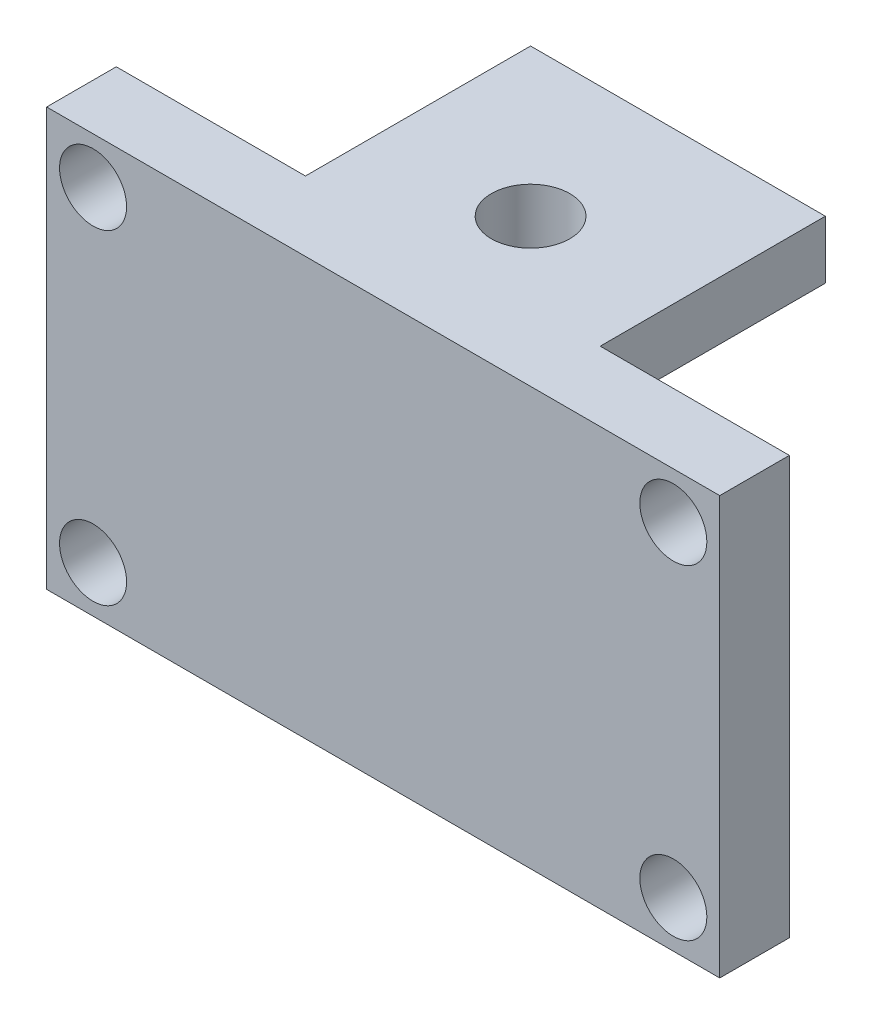
SolidWorks part; units mm, degrees
ref_plane "Front Plane" through (0, 0, 0) normal (0, 0, 1) x (1, 0, 0)
ref_plane "Top Plane" through (0, 0, 0) normal (0, 1, 0) x (1, 0, 0)
ref_plane "Right Plane" through (0, 0, 0) normal (1, 0, 0) x (0, 0, -1)
sketch "Sketch1" plane through (0, 0, 0) normal (0, 1, 0) x (1, 0, 0)
  line L1 (-12.7, 12.7) -> (12.7, 12.7)
  line L2 (-12.7, 12.7) -> (-12.7, -12.7)
  line L3 (-12.7, -12.7) -> (12.7, -12.7)
  line L4 (12.7, 12.7) -> (12.7, -12.7)
  line L5 (-12.7, 12.7) -> (12.7, -12.7) construction
  line L6 (-12.7, -12.7) -> (12.7, 12.7) construction
  point P0 (0, 0)
  dimension "D1" = 25.4
  dimension "D2" = 25.4
extrude "Boss-Extrude1" add sketch "Sketch1" along normal blind 5
hole_wizard "1/4 Clearance Hole1" positions "Sketch2" profile "Sketch3" hole size "1/4" standard "ANSI Inch" end condition through all
sketch "Sketch2" plane through (0, 5, 0) normal (0, 1, 0) x (1, 0, 0)
  point P0 (0, 0)
sketch "Sketch3" plane through (0, 5, 0) normal (1, 0, 0) x (0, 0, 1)
  line L0 (0, 0) -> (0, 5)
  line L1 (0, 5) -> (3.3782, 5)
  line L2 (3.3782, 5) -> (3.3782, 0)
  line L5 (3.3782, 0) -> (0, 0)
  line L11 (0, -6.35) -> (0, 107.95) construction
  dimension "Thru Hole Dia." = 6.7564
  dimension "Thru Hole Depth" = 5
sketch "Sketch4" plane through (0, 0, 12.7) normal (0, 0, 1) x (1, 0, 0)
  line L0 (-29, -31) -> (-29, 5)
  line L1 (-25, -27) -> (25, -27) construction
  line L2 (-25, -27) -> (-25, 1) construction
  line L3 (-25, 1) -> (25, 1) construction
  line L4 (25, -27) -> (25, 1) construction
  line L5 (-25, -27) -> (25, 1) construction
  line L6 (-25, 1) -> (25, -27) construction
  line L7 (-29, 5) -> (29, 5)
  line L8 (29, -31) -> (29, 5)
  line L9 (-29, -31) -> (29, -31)
  line L10 (-12.7, 5) -> (12.7, 5) construction
  circle A0 centre (-25, 1) radius 2.8879
  circle A1 centre (25, 1) radius 2.8879
  circle A2 centre (25, -27) radius 2.8879
  circle A3 centre (-25, -27) radius 2.8879
  point P0 (0, -13)
  line M9 (-12.7, 0) -> (12.7, 0)
  line M10 (12.7, 0) -> (12.7, 5)
  line M12 (-12.7, 5) -> (-12.7, 0)
  dimension "D1" = 4
  dimension "D2" = 50
  dimension "D3" = 28
extrude "Boss-Extrude2" add sketch "Sketch4" against normal blind 6 contours L0 L9 L8 L7 A3 A2 A1 A0 M10 M9 M12 region at (0, -14.0605, 12.7)
